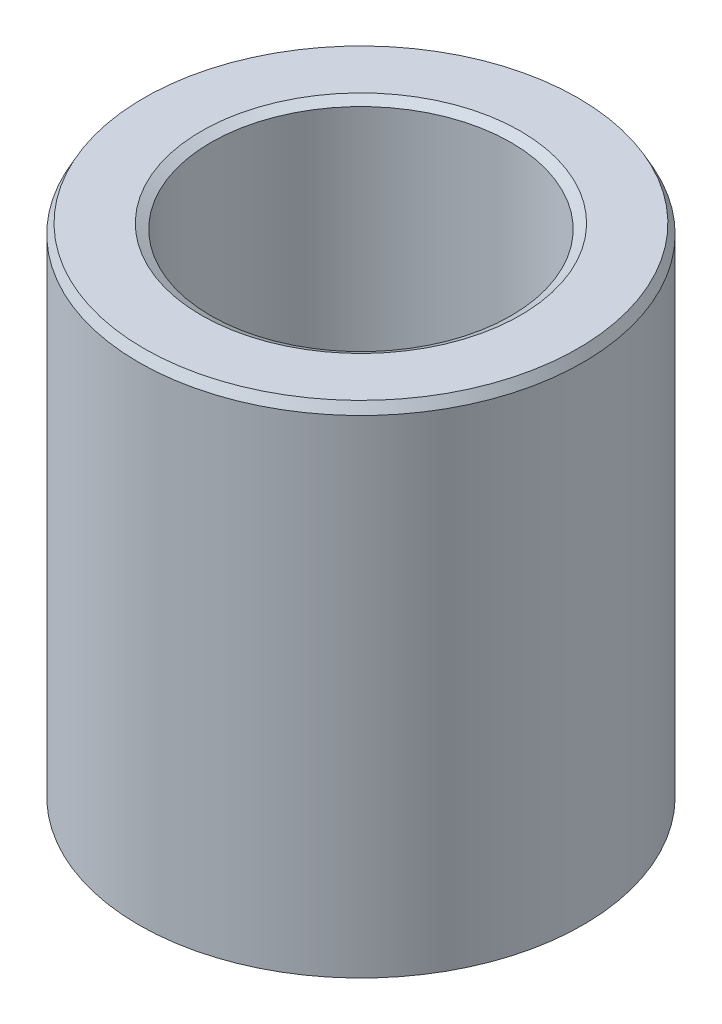
SolidWorks part; units mm, degrees
ref_plane "Front Plane" through (0, 0, 0) normal (0, 0, 1) x (1, 0, 0)
ref_plane "Top Plane" through (0, 0, 0) normal (0, 1, 0) x (1, 0, 0)
ref_plane "Right Plane" through (0, 0, 0) normal (1, 0, 0) x (0, 0, -1)
sketch "Sketch1" plane through (0, 0, 0) normal (0, 1, 0) x (1, 0, 0)
  circle A0 centre (0, 0) radius 57.5
  dimension "SLEEVE_OD" = 115
extrude "Boss-Extrude1" add sketch "Sketch1" along normal blind 129.854
sketch "Sketch2" plane through (0, 0, 0) normal (0, 1, 0) x (1, 0, 0)
  circle A0 centre (0, 0) radius 38.8419
  dimension "BORE_D" = 77.6838
extrude "Cut-Extrude1" cut sketch "Sketch2" along normal through all
chamfer "Chamfer1" distance 2.4517 angle 28.435 4 edges at (0, 129.854, 38.8419) (0, 0, 38.8419) (0, 0, 57.5) (0, 129.854, 57.5) first distance on face at (0, 129.854, 38.8419) first distance on face at (0, 0, 38.8419) first distance on face at (0, 129.854, 57.5)
